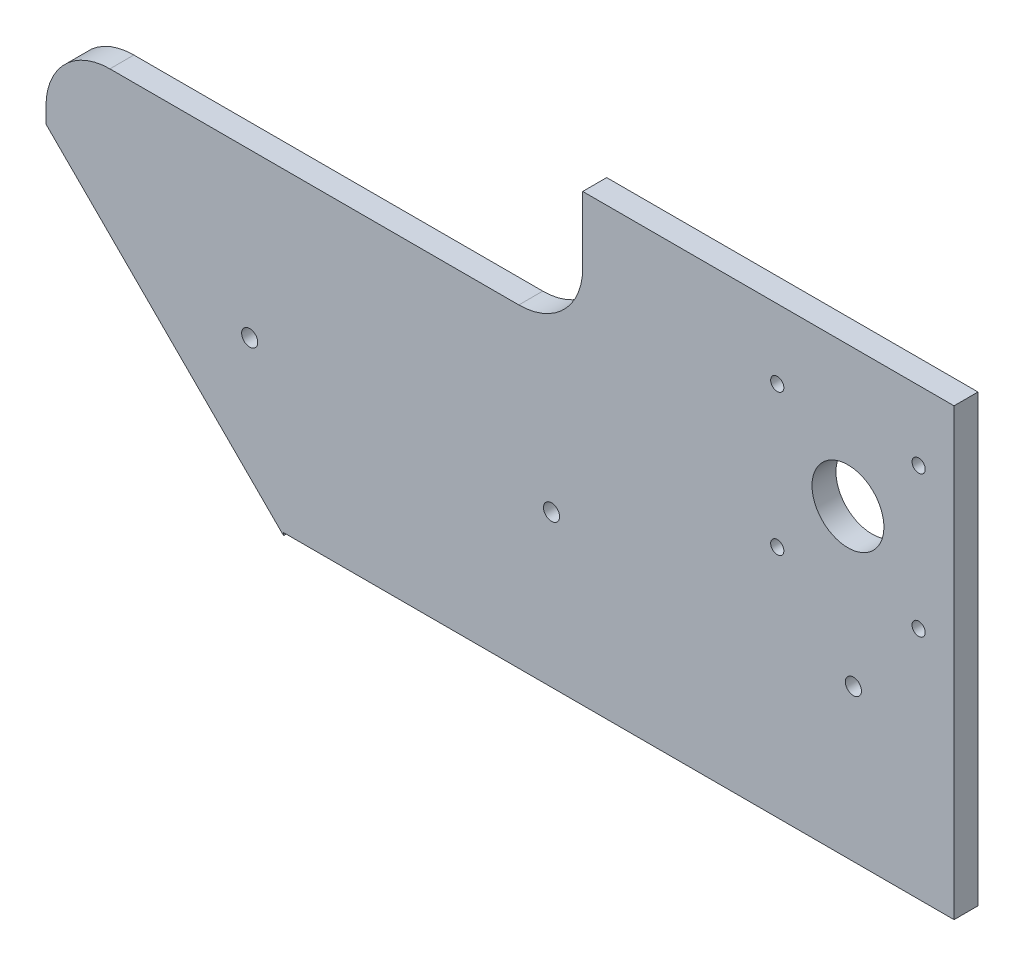
SolidWorks part; units mm, degrees
ref_plane "Front Plane" through (0, 0, 0) normal (0, 0, 1) x (1, 0, 0)
ref_plane "Top Plane" through (0, 0, 0) normal (0, 1, 0) x (1, 0, 0)
ref_plane "Right Plane" through (0, 0, 0) normal (1, 0, 0) x (0, 0, -1)
sketch "Sketch1" plane through (0, 0, 0) normal (0, 0, 1) x (1, 0, 0)
  line L0 (-138.2594, 48.9915) -> (32.2106, -121.4785)
  line L1 (32.2106, -121.4785) -> (222.7106, -121.4785)
  line L2 (-138.2594, 146.2068) -> (-138.2594, 48.9915)
  line L3 (-138.2594, 146.2068) -> (222.7106, 146.2068)
  line L4 (222.7106, -121.4785) -> (222.7106, 146.2068)
  circle A0 centre (180.538, 76.832) radius 14.2875
  circle A2 centre (180.538, 76.832) radius 69.85 construction
  circle A3 centre (180.538, 76.832) radius 318.7974 construction
  point P0 (0, 0)
  point P2 (180.538, 76.832)
  dimension "D4" = 198.3105
  dimension "D1" = 45
  dimension "D2" = 267.6854
  dimension "D5" = 245.11
extrude "Boss-Extrude1" add sketch "Sketch1" along normal blind 9.525
sketch "Sketch2" plane through (0, 0, 9.525) normal (0, 0, 1) x (1, 0, 0)
  line L0 (32.2106, -121.4785) -> (222.7106, -121.4785) construction
  line L1 (241.7606, -121.4785) -> (-43.8123, -121.4785)
  line L2 (241.7606, -121.4785) -> (241.7606, -44.3895)
  line L3 (241.7606, -44.3895) -> (-43.8123, -44.3895)
  line L4 (-43.8123, -121.4785) -> (-43.8123, -44.3895)
extrude "Cut-Extrude1" cut sketch "Sketch2" against normal through all contours L3 L4 L1 L2
sketch "Sketch4" plane through (0, 0, 9.525) normal (0, 0, 1) x (1, 0, 0)
  line L1 (-138.2594, 146.2068) -> (-138.2594, 48.9915) construction
  line L3 (-138.2594, 146.2068) -> (75.1006, 146.2068)
  line L4 (-138.2594, 146.2068) -> (-138.2594, 80.7415)
  line L5 (-138.2594, 80.7415) -> (75.1006, 80.7415)
  line L6 (75.1006, 146.2068) -> (75.1006, 80.7415)
extrude "Cut-Extrude2" cut sketch "Sketch4" against normal through all contours L5 L6 L3 L4
fillet "Fillet2" radius 25.4 2 edges at (-138.2594, 80.7415, 4.7625) (75.1006, 80.7415, 4.7625)
sketch "Sketch16" plane through (222.7106, 0, 0) normal (1, 0, 0) x (0, 0, -1)
  line L0 (0, -44.3895) -> (0, 146.2068) construction
  line L1 (-9.525, 146.2068) -> (0, 146.2068)
  line L2 (-9.525, 146.2068) -> (-9.525, 145.2215)
  line L3 (-9.525, 145.2215) -> (0, 145.2215)
  line L4 (0, 146.2068) -> (0, 145.2215)
extrude "Cut-Extrude3" cut sketch "Sketch16" against normal through all
sketch "Sketch17" plane through (0, 0, 0) normal (0, 0, -1) x (-1, 0, 0)
  line L0 (-222.7106, -44.3895) -> (-222.7106, 145.2215) construction
  line L1 (-75.1006, 145.2215) -> (-222.7106, 145.2215)
  line L2 (-75.1006, 145.2215) -> (-75.1006, 132.5215)
  line L3 (-75.1006, 132.5215) -> (-222.7106, 132.5215)
  line L4 (-222.7106, 145.2215) -> (-222.7106, 132.5215)
  dimension "D1" = 12.7
extrude "Cut-Extrude4" cut sketch "Sketch17" against normal through all
hole_wizard "Tap Drill for M6x0.75 Tap1" positions "Sketch19" profile "Sketch18" hole size "M6x0.75" standard "Lanco STD" end condition through all
sketch "Sketch19" plane through (0, 0, 9.525) normal (0, 0, 1) x (1, 0, 0)
  point P0 (208.638, 104.932)
  point P3 (152.438, 104.932)
  point P6 (152.438, 48.732)
  point P9 (208.638, 48.732)
sketch "Sketch18" plane through (208.638, 104.932, 9.525) normal (1, 0, 0) x (0, -1, 0)
  line L0 (0, 0) -> (0, 9.525)
  line L1 (0, 9.525) -> (2.625, 9.525)
  line L2 (2.625, 9.525) -> (2.625, 0)
  line L5 (2.625, 0) -> (0, 0)
  line L11 (0, -6.35) -> (0, 107.95) construction
  dimension "Thru Hole Dia." = 5.25
  dimension "Thru Hole Depth" = 9.525
hole_wizard "Ø6.4 (6.4) Diameter Hole1" positions "Sketch21" profile "Sketch20" hole size "Ø6.4" standard "ANSI Metric" end condition through all
sketch "Sketch21" plane through (0, 0, 9.525) normal (0, 0, 1) x (1, 0, 0)
  point P0 (-57.2894, 15.9355)
  point P2 (62.7106, 15.9355)
  point P4 (182.7106, 15.9355)
sketch "Sketch20" plane through (-57.2894, 15.9355, 9.525) normal (1, 0, 0) x (0, -1, 0)
  line L0 (0, 0) -> (0, 9.525)
  line L1 (0, 9.525) -> (3.2, 9.525)
  line L2 (3.2, 9.525) -> (3.2, 0)
  line L5 (3.2, 0) -> (0, 0)
  line L11 (0, -6.35) -> (0, 107.95) construction
  dimension "Thru Hole Dia." = 6.4
  dimension "Thru Hole Depth" = 9.525
